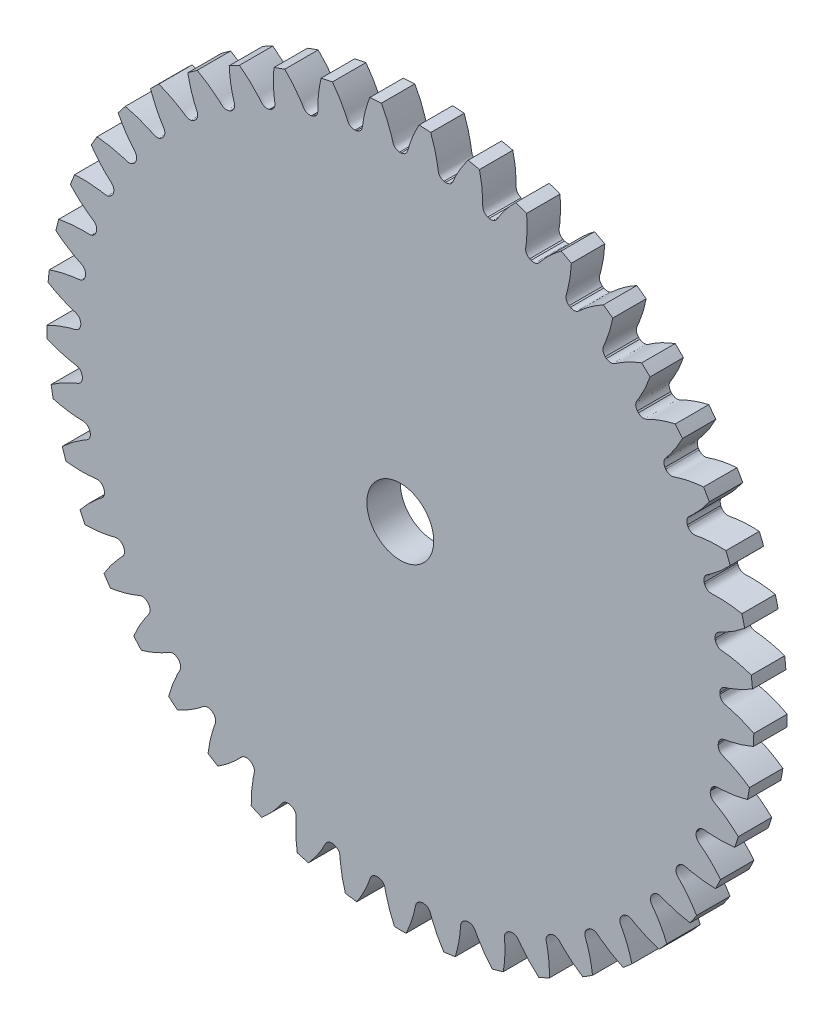
SolidWorks part; units mm, degrees
ref_plane "前视基准面" through (0, 0, 0) normal (0, 0, 1) x (1, 0, 0)
ref_plane "上视基准面" through (0, 0, 0) normal (0, 1, 0) x (1, 0, 0)
ref_plane "右视基准面" through (0, 0, 0) normal (1, 0, 0) x (0, 0, -1)
other "Configuration Table"
sketch "草图1" plane through (0, 0, 0) normal (0, 0, 1) x (1, 0, 0)
  circle A0 centre (0, 0) radius 10.575
extrude "凸台-拉伸1" add sketch "草图1" along normal blind 1
ref_axis "基准轴1" through (0, 0, 1) along (0, 0, -1)
sketch "草图2" plane through (0, 0, 0) normal (0, 0, 1) x (1, 0, 0)
  line L0 (0, 0) -> (0, 10.575) construction
  circle A0 centre (0, 0) radius 10.575 construction
  arc A1 (0.0233, 9.5625) -> (-0.0233, 9.5625) centre (0, 0) ccw
  arc A2 (1.7228, 12.0175) -> (-1.7228, 12.0175) centre (0, 0) ccw
  spline S0 degree 3 poles (0.0233, 9.5625) (0.1996, 9.5868) (0.2196, 9.7176) (0.2613, 9.8593) (0.2773, 9.9107) (0.2956, 9.9653) (0.3162, 10.0231) (0.3393, 10.084) (0.3651, 10.148) (0.3937, 10.215) (0.4251, 10.2849) (0.4596, 10.3575) (0.4972, 10.4329) (0.538, 10.5109) (0.5823, 10.5913) (0.63, 10.6742) (0.6814, 10.7593) (0.7365, 10.8467) (0.7954, 10.9361) (0.8583, 11.0274) (0.9252, 11.1205) (0.9962, 11.2154) (1.0714, 11.3118) (1.151, 11.4096) (1.2349, 11.5087) (1.3233, 11.609) (1.4163, 11.7103) (1.5483, 11.8483) (1.6517, 11.9502) (1.7228, 12.0175) knots 0 0 0 0 0.112268 0.128789 0.146568 0.165606 0.185901 0.207456 0.230268 0.254339 0.279668 0.306255 0.334101 0.363205 0.393567 0.425188 0.458067 0.492204 0.527599 0.564253 0.602166 0.641336 0.681765 0.723452 0.766398 0.810601 0.856064 0.902784 1 1 1 1
  spline S1 degree 3 poles (-0.0233, 9.5625) (-0.1996, 9.5868) (-0.2196, 9.7176) (-0.2613, 9.8593) (-0.2773, 9.9107) (-0.2956, 9.9653) (-0.3162, 10.0231) (-0.3393, 10.084) (-0.3651, 10.148) (-0.3937, 10.215) (-0.4251, 10.2849) (-0.4596, 10.3575) (-0.4972, 10.4329) (-0.538, 10.5109) (-0.5823, 10.5913) (-0.63, 10.6742) (-0.6814, 10.7593) (-0.7365, 10.8467) (-0.7954, 10.9361) (-0.8583, 11.0274) (-0.9252, 11.1205) (-0.9962, 11.2154) (-1.0714, 11.3118) (-1.151, 11.4096) (-1.2349, 11.5087) (-1.3233, 11.609) (-1.4163, 11.7103) (-1.5483, 11.8483) (-1.6517, 11.9502) (-1.7228, 12.0175) knots 0 0 0 0 0.112268 0.128789 0.146568 0.165606 0.185901 0.207456 0.230268 0.254339 0.279668 0.306255 0.334101 0.363205 0.393567 0.425188 0.458067 0.492204 0.527599 0.564253 0.602166 0.641336 0.681765 0.723452 0.766398 0.810601 0.856064 0.902784 1 1 1 1
extrude "切除-拉伸1" cut sketch "草图2" along normal through all
pattern_circular "阵列(圆周)1" count 45 every 8 about axis through (0, 0, 1) along (0, 0, -1) of "切除-拉伸1"
sketch "草图3" plane through (0, 0, 0) normal (0, 0, 1) x (1, 0, 0)
  circle A0 centre (0, 0) radius 10.125 construction
  dimension "Dn" = 20.25
sketch "草图4" plane through (0, 0, 1) normal (0, 0, 1) x (1, 0, 0)
  circle A0 centre (0, 0) radius 1
  dimension "D1" = 2
extrude "切除-拉伸2" cut sketch "草图4" against normal through all
